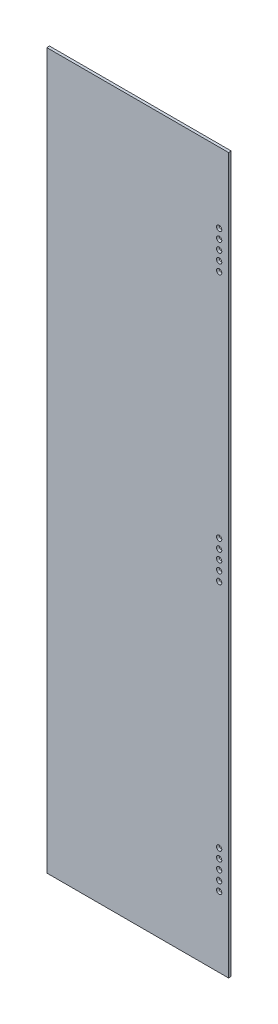
SolidWorks part; units mm, degrees
material "1060 Alloy"
ref_plane "Front Plane" through (0, 0, 0) normal (0, 0, 1) x (1, 0, 0)
ref_plane "Top Plane" through (0, 0, 0) normal (0, 1, 0) x (1, 0, 0)
ref_plane "Right Plane" through (0, 0, 0) normal (1, 0, 0) x (0, 0, -1)
sketch "Sketch1" plane through (0, 0, 0) normal (0, 0, 1) x (1, 0, 0)
  line L1 (-77.5, 304.8) -> (77.5, 304.8)
  line L2 (-77.5, 304.8) -> (-77.5, -304.8)
  line L3 (-77.5, -304.8) -> (77.5, -304.8)
  line L4 (77.5, 304.8) -> (77.5, -304.8)
  line L5 (-77.5, 304.8) -> (77.5, -304.8) construction
  line L6 (-77.5, -304.8) -> (77.5, 304.8) construction
  point P0 (0, 0)
  point P5 (69.5, 244.8)
  point P7 (69.5, 228.8)
  point P8 (69.5, 236.8)
  point P9 (69.5, 220.8)
  point P10 (69.5, 212.8)
  point P11 (69.5, 8)
  point P12 (69.5, 16)
  point P13 (69.5, -212.8)
  point P14 (69.5, -228.8)
  point P15 (69.5, -220.8)
  point P16 (69.5, -236.8)
  point P17 (69.5, -244.8)
  point P18 (69.5, -8)
  point P19 (69.5, -16)
  point P20 (0, 0)
  point P21 (0, 0)
  point P22 (69.5, 0)
  dimension "D1" = 609.6
  dimension "D2" = 155
  dimension "D3" = 8
  dimension "D4" = 60
  dimension "D5" = 8
  dimension "D6" = 8
  dimension "D7" = 8
  dimension "D8" = 8
  dimension "D9" = 60
  dimension "D10" = 8
  dimension "D11" = 8
  dimension "D12" = 8
  dimension "D13" = 8
  dimension "D14" = 8
  dimension "D15" = 8
  dimension "D16" = 8
  dimension "D17" = 8
  dimension "D18" = 8
  dimension "D19" = 8
extrude "Boss-Extrude1" add sketch "Sketch1" along normal blind 2.305
hole_wizard "M4 Clearance Hole1" positions "Sketch3" profile "Sketch5" hole size "M4" standard "ANSI Metric" end condition through all
sketch "Sketch3" plane through (0, 0, 2.305) normal (0, 0, 1) x (1, 0, 0)
  point P4 (69.5, 228.8)
  point P9 (69.5, 244.8)
  point P12 (69.5, 236.8)
  point P15 (69.5, 220.8)
  point P18 (69.5, 212.8)
  point P21 (69.5, 16)
  point P24 (69.5, 8)
  point P27 (69.5, 0)
  point P30 (69.5, -8)
  point P33 (69.5, -16)
  point P36 (69.5, -212.8)
  point P39 (69.5, -220.8)
  point P42 (69.5, -228.8)
  point P45 (69.5, -236.8)
  point P48 (69.5, -244.8)
sketch "Sketch5" plane through (69.5, 228.8, 2.305) normal (1, 0, 0) x (0, -1, 0)
  line L0 (0, 0) -> (0, 2.305)
  line L1 (0, 2.305) -> (2.25, 2.305)
  line L2 (2.25, 2.305) -> (2.25, 0)
  line L5 (2.25, 0) -> (0, 0)
  line L11 (0, -6.35) -> (0, 107.95) construction
  dimension "Thru Hole Dia." = 4.5
  dimension "Thru Hole Depth" = 2.305
